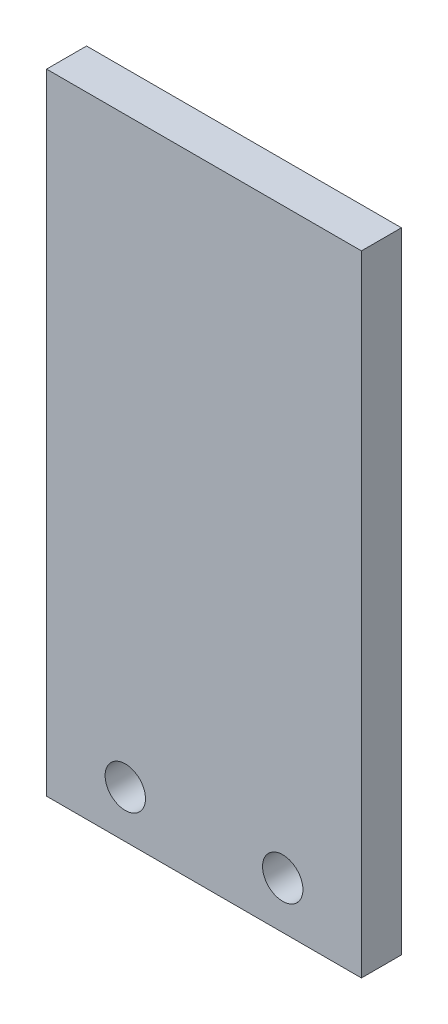
SolidWorks part; units mm, degrees
ref_plane "Front Plane" through (0, 0, 0) normal (0, 0, 1) x (1, 0, 0)
ref_plane "Top Plane" through (0, 0, 0) normal (0, 1, 0) x (1, 0, 0)
ref_plane "Right Plane" through (0, 0, 0) normal (1, 0, 0) x (0, 0, -1)
sketch "Sketch1" plane through (0, 0, 0) normal (0, 0, 1) x (1, 0, 0)
  line L1 (0, 0) -> (100, 0)
  line L2 (0, 0) -> (0, 200)
  line L3 (0, 200) -> (100, 200)
  line L4 (100, 0) -> (100, 200)
  dimension "D1" = 100
  dimension "D2" = 200
extrude "Boss-Extrude1" add sketch "Sketch1" along normal blind 12.7
hole_wizard "1/2 (0.5) Diameter Hole1" positions "Sketch5" profile "Sketch4" hole size "1/2" standard "ANSI Inch" end condition through all
sketch "Sketch5" plane through (0, 0, 12.7) normal (0, 0, 1) x (1, 0, 0)
  point P0 (75, 15)
  point P2 (25, 15)
  dimension "D1" = 25
  dimension "D2" = 25
  dimension "D3" = 50
  dimension "D4" = 15
sketch "Sketch4" plane through (75, 15, 12.7) normal (1, 0, 0) x (0, -1, 0)
  line L0 (0, 0) -> (0, 12.7)
  line L1 (0, 12.7) -> (6.4135, 12.7)
  line L2 (6.4135, 12.7) -> (6.4135, 0)
  line L5 (6.4135, 0) -> (0, 0)
  line L11 (0, -6.35) -> (0, 107.95) construction
  dimension "Thru Hole Dia." = 12.827
  dimension "Thru Hole Depth" = 12.7
equation "\"Plate_Height\"= 0.2m"
equation "\"Plate_Width\"= 0.1m"
equation "\"Plate_Thickness\"= 0.00635 * 2m"
